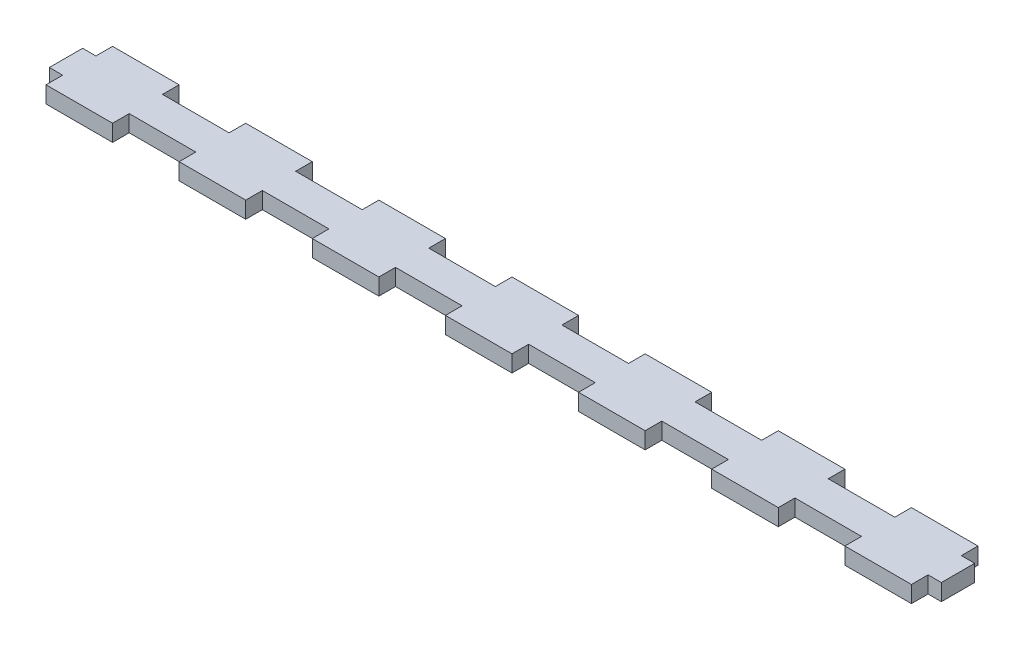
SolidWorks part; units mm, degrees
material "Maple"
ref_plane "Front Plane" through (0, 0, 0) normal (0, 0, 1) x (1, 0, 0)
ref_plane "Top Plane" through (0, 0, 0) normal (0, 1, 0) x (1, 0, 0)
ref_plane "Right Plane" through (0, 0, 0) normal (1, 0, 0) x (0, 0, -1)
sketch "Sketch1" plane through (0, 0, 0) normal (0, 1, 0) x (1, 0, 0)
  line L0 (0, 5) -> (-67, 5) construction
  line L5 (0, 0) -> (-67, 0) construction
  line L6 (0, 0) -> (0, 2.5) construction
  line L7 (0, 2.5) -> (-67, 2.5) construction
  line L8 (-67, 0) -> (-67, 2.5) construction
  line L9 (-67, 2.5) -> (-65, 2.5)
  line L10 (-65, 2.5) -> (-65, 5)
  line L11 (-65, 5) -> (-55, 5)
  line L12 (-55, 5) -> (-55, 2.5)
  line L13 (-55, 2.5) -> (-45, 2.5)
  line L14 (-45, 2.5) -> (-45, 5)
  line L15 (-45, 5) -> (-35, 5)
  line L16 (-35, 5) -> (-35, 2.5)
  line L17 (-35, 2.5) -> (-25, 2.5)
  line L18 (-25, 2.5) -> (-25, 5)
  line L19 (-25, 5) -> (-15, 5)
  line L20 (-15, 5) -> (-15, 2.5)
  line L21 (-15, 2.5) -> (-5, 2.5)
  line L22 (-5, 2.5) -> (-5, 5)
  line L23 (-5, 5) -> (5, 5)
  line L24 (-67, 2.5) -> (-67, -2.5)
  line L25 (-67, -2.5) -> (-65, -2.5)
  line L26 (-65, -2.5) -> (-65, -5)
  line L27 (-65, -5) -> (-55, -5)
  line L28 (-55, -5) -> (-55, -2.5)
  line L29 (-55, -2.5) -> (-45, -2.5)
  line L30 (-45, -2.5) -> (-45, -5)
  line L31 (-45, -5) -> (-35, -5)
  line L32 (-35, -5) -> (-35, -2.5)
  line L33 (-35, -2.5) -> (-25, -2.5)
  line L34 (-25, -2.5) -> (-25, -5)
  line L35 (-25, -5) -> (-15, -5)
  line L36 (-15, -5) -> (-15, -2.5)
  line L37 (-15, -2.5) -> (-5, -2.5)
  line L38 (-5, -2.5) -> (-5, -5)
  line L39 (-5, -5) -> (5, -5)
  line L40 (5, -2.5) -> (5, -5)
  line L41 (15, -2.5) -> (5, -2.5)
  line L42 (15, -5) -> (15, -2.5)
  line L43 (25, -5) -> (15, -5)
  line L44 (25, -2.5) -> (25, -5)
  line L45 (35, -2.5) -> (25, -2.5)
  line L46 (35, -5) -> (35, -2.5)
  line L47 (45, -5) -> (35, -5)
  line L48 (45, -2.5) -> (45, -5)
  line L49 (55, -2.5) -> (45, -2.5)
  line L50 (55, -5) -> (55, -2.5)
  line L51 (65, -5) -> (55, -5)
  line L52 (65, -2.5) -> (65, -5)
  line L53 (67, -2.5) -> (65, -2.5)
  line L54 (67, 2.5) -> (67, -2.5)
  line L55 (67, 2.5) -> (65, 2.5)
  line L56 (65, 2.5) -> (65, 5)
  line L57 (65, 5) -> (55, 5)
  line L58 (55, 5) -> (55, 2.5)
  line L59 (55, 2.5) -> (45, 2.5)
  line L60 (45, 2.5) -> (45, 5)
  line L61 (45, 5) -> (35, 5)
  line L62 (35, 5) -> (35, 2.5)
  line L63 (35, 2.5) -> (25, 2.5)
  line L64 (25, 2.5) -> (25, 5)
  line L65 (25, 5) -> (15, 5)
  line L66 (15, 5) -> (15, 2.5)
  line L67 (15, 2.5) -> (5, 2.5)
  line L68 (5, 2.5) -> (5, 5)
  point P39 (0, -5)
  dimension "D1" = 2.5
  dimension "D2" = 10
  dimension "D3" = 2
  dimension "D4" = 10
extrude "Boss-Extrude1" add sketch "Sketch1" along normal mid plane 2.5
